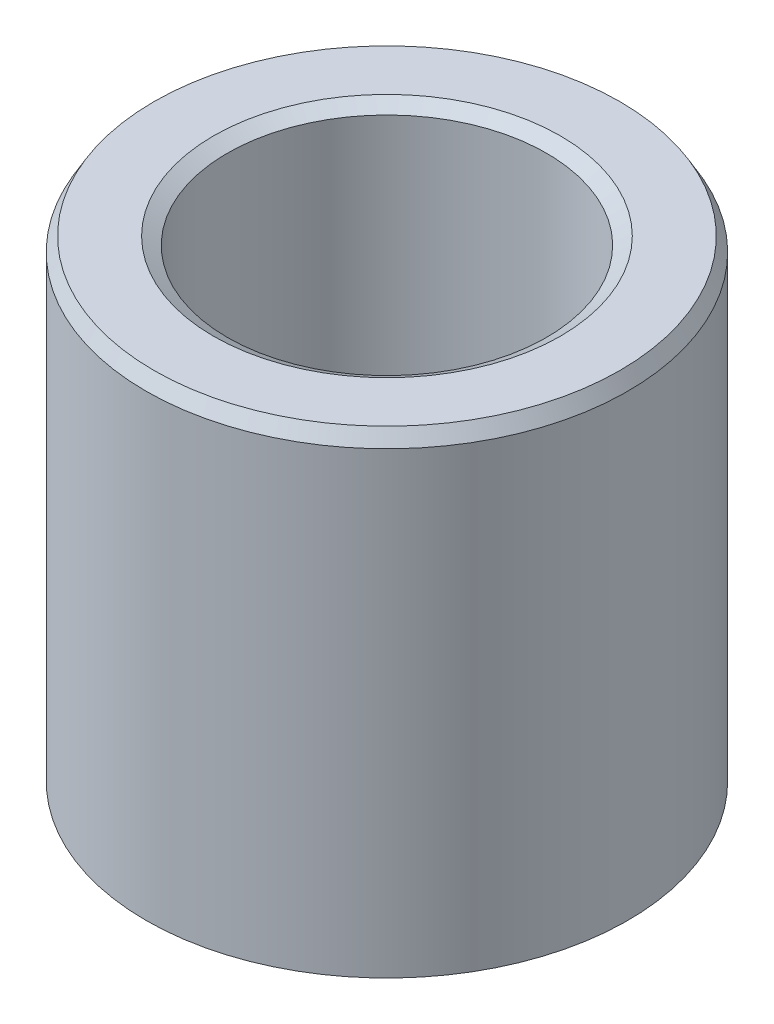
SolidWorks part; units mm, degrees
ref_plane "Front Plane" through (0, 0, 0) normal (0, 0, 1) x (1, 0, 0)
ref_plane "Top Plane" through (0, 0, 0) normal (0, 1, 0) x (1, 0, 0)
ref_plane "Right Plane" through (0, 0, 0) normal (1, 0, 0) x (0, 0, -1)
sketch "Sketch1" plane through (0, 0, 0) normal (0, 1, 0) x (1, 0, 0)
  circle A0 centre (0, 0) radius 55
  dimension "SLEEVE_OD" = 110
extrude "Boss-Extrude1" add sketch "Sketch1" along normal blind 109.6342
sketch "Sketch2" plane through (0, 0, 0) normal (0, 1, 0) x (1, 0, 0)
  circle A0 centre (0, 0) radius 36.4362
  dimension "BORE_D" = 72.8723
extrude "Cut-Extrude1" cut sketch "Sketch2" along normal through all
chamfer "Chamfer1" distance 3.1707 angle 30 4 edges at (0, 109.6342, 36.4362) (0, 0, 36.4362) (0, 0, 55) (0, 109.6342, 55) first distance on face at (0, 109.6342, 36.4362) first distance on face at (0, 0, 36.4362) first distance on face at (0, 109.6342, 55)
